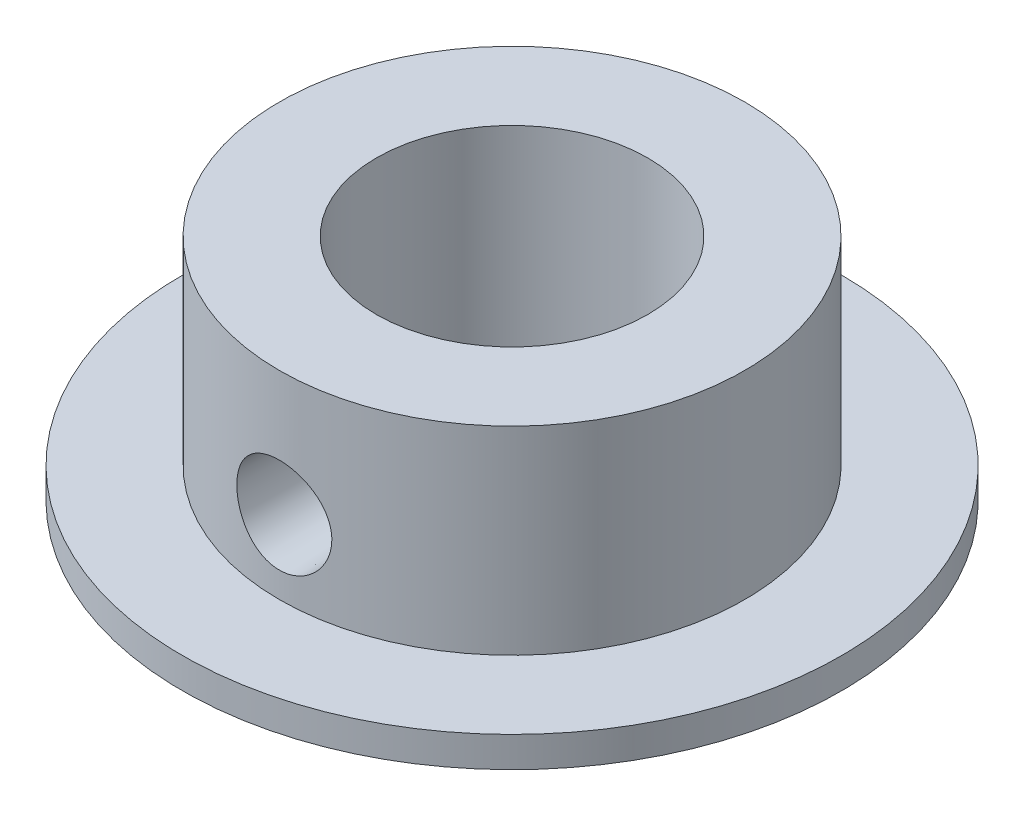
SolidWorks part; units mm, degrees
ref_plane "Front Plane" through (0, 0, 0) normal (0, 0, 1) x (1, 0, 0)
ref_plane "Top Plane" through (0, 0, 0) normal (0, 1, 0) x (1, 0, 0)
ref_plane "Right Plane" through (0, 0, 0) normal (1, 0, 0) x (0, 0, -1)
sketch "Sketch1" plane through (0, 0, 0) normal (0, 0, 1) x (1, 0, 0)
  line L0 (-17.78, 0) -> (-17.78, 30)
  line L1 (-17.78, 30) -> (-30.48, 30)
  line L2 (-30.48, 30) -> (-30.48, 4)
  line L3 (-30.48, 4) -> (-43.18, 4)
  line L4 (-43.18, 4) -> (-43.18, 0)
  line L5 (-43.18, 0) -> (-17.78, 0)
  line L6 (0, 0) -> (0, 13.053) construction
  dimension "D1" = 17.78
  dimension "D2" = 30
  dimension "D3" = 12.7
  dimension "D4" = 12.7
  dimension "D5" = 4
revolve "Revolve1" add sketch "Sketch1" angle 360 about L6
ref_plane "Plane1" through (0, 0, 30.48) normal (0, 0, 1) x (1, 0, 0)
hole_wizard "1/4 NPT Tapped Hole1" positions "Sketch2" profile "Sketch3" size "1/4" standard "ANSI Inch" end condition up to next
sketch "Sketch2" plane through (0, 0, 30.48) normal (0, 0, 1) x (1, 0, 0)
  point P0 (0, 13.5907)
sketch "Sketch3" plane through (0, 13.5907, 30.48) normal (1, 0, 0) x (0, -1, 0)
  line L0 (0, 0) -> (0, 12.7)
  line L1 (0, 12.7) -> (5.5626, 12.7)
  line L2 (-5.9437, 10.02) -> (-6.2437, 0) construction
  line L3 (5.5626, 12.7) -> (5.5626, 10.02)
  line L4 (5.5626, 10.02) -> (5.9437, 10.02)
  line L5 (5.9437, 10.02) -> (6.2437, 0)
  line L7 (6.2437, 0) -> (0, 0)
  line L8 (0, -6.35) -> (0, 107.95) construction
  line L11 (-5.5626, 10.02) -> (-5.9437, 10.02) construction
  dimension "Thru Tap Drill Dia." = 11.1252
  dimension "Thru Tap Drill Depth" = 12.7
  dimension "Thread Dia." = 12.4874
  dimension "Thread Angle" = 3.43
  dimension "Thread Depth" = 10.02
cosmetic thread "Hole Thread1" parameters "D1"=10.02, "D2"=13.716
